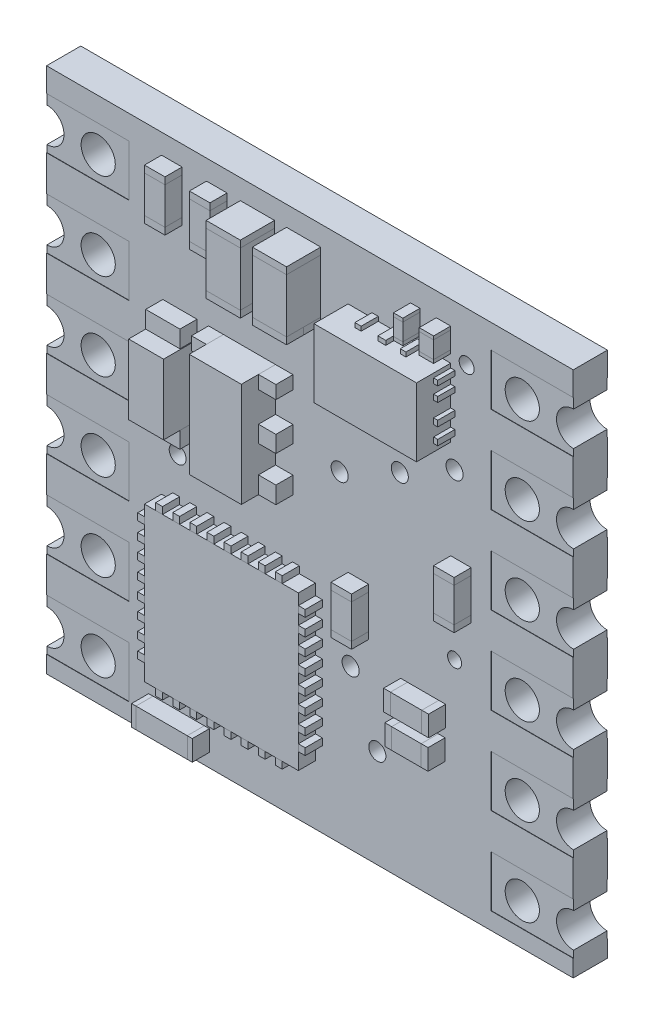
SolidWorks part; units mm, degrees
ref_plane "前视基准面" through (0, 0, 0) normal (0, 0, 1) x (1, 0, 0)
ref_plane "上视基准面" through (0, 0, 0) normal (0, 1, 0) x (1, 0, 0)
ref_plane "右视基准面" through (0, 0, 0) normal (1, 0, 0) x (0, 0, -1)
sketch "草图1" plane through (0, 0, 0) normal (0, 0, 1) x (1, 0, 0)
  line L1 (-7.7, 7.7) -> (7.7, 7.7)
  line L2 (-7.7, 7.7) -> (-7.7, -7.7)
  line L3 (-7.7, -7.7) -> (7.7, -7.7)
  line L4 (7.7, 7.7) -> (7.7, -7.7)
  line L5 (-7.7, 7.7) -> (7.7, -7.7) construction
  line L6 (-7.7, -7.7) -> (7.7, 7.7) construction
  point P0 (0, 0)
extrude "凸台-拉伸1" add sketch "草图1" along normal blind 1
sketch "草图2" plane through (0, 0, 1) normal (0, 0, 1) x (1, 0, 0)
  line L0 (-6.2, 7.7) -> (-6.2, -7.7) construction
  line L1 (7.7, 7.7) -> (-7.7, 7.7) construction
  line L2 (-7.7, -7.7) -> (7.7, -7.7) construction
  line L3 (0, 7.7) -> (0, -7.7) construction
  line L4 (-7.7, 7.7) -> (-7.7, -7.7) construction
  circle A0 centre (-6.2, 6.2) radius 0.5
  circle A1 centre (-6.2, 3.66) radius 0.5
  circle A2 centre (-6.2, 1.12) radius 0.5
  circle A3 centre (-6.2, -1.42) radius 0.5
  circle A4 centre (-6.2, -3.96) radius 0.5
  circle A5 centre (-6.2, -6.5) radius 0.5
  circle A6 centre (-7.7, 6.2) radius 0.5
  circle A7 centre (-7.7, 3.66) radius 0.5
  circle A8 centre (-7.7, 1.12) radius 0.5
  circle A9 centre (-7.7, -1.42) radius 0.5
  circle A10 centre (-7.7, -3.96) radius 0.5
  circle A11 centre (-7.7, -6.5) radius 0.5
  circle A12 centre (7.7, -6.5) radius 0.5
  circle A13 centre (7.7, -3.96) radius 0.5
  circle A14 centre (7.7, -1.42) radius 0.5
  circle A15 centre (7.7, 1.12) radius 0.5
  circle A16 centre (7.7, 3.66) radius 0.5
  circle A17 centre (7.7, 6.2) radius 0.5
  circle A18 centre (6.2, -6.5) radius 0.5
  circle A19 centre (6.2, -3.96) radius 0.5
  circle A20 centre (6.2, -1.42) radius 0.5
  circle A21 centre (6.2, 1.12) radius 0.5
  circle A22 centre (6.2, 3.66) radius 0.5
  circle A23 centre (6.2, 6.2) radius 0.5
  dimension "D2" = 1.5
  dimension "D4" = 6
  dimension "D1" = 1.5
  dimension "D3" = 6
extrude "切除-拉伸1" cut sketch "草图2" against normal blind 1
sketch "草图3" plane through (0, 0, 1) normal (0, 0, 1) x (1, 0, 0)
  line L0 (-7.7, 7.7) -> (-7.7, 6.7) construction
  line L1 (-7.7, 6.9978) -> (-5.2945, 6.9978)
  line L2 (-7.7, 6.9978) -> (-7.7, 5.4978)
  line L3 (-7.7, 5.4978) -> (-5.2945, 5.4978)
  line L4 (-5.2945, 6.9978) -> (-5.2945, 5.4978)
  line L5 (-7.7, 4.4578) -> (-5.2945, 4.4578)
  line L6 (-7.7, 4.4578) -> (-7.7, 2.9578)
  line L7 (-7.7, 2.9578) -> (-5.2945, 2.9578)
  line L8 (-5.2945, 4.4578) -> (-5.2945, 2.9578)
  line L9 (-7.7, 1.9178) -> (-5.2945, 1.9178)
  line L10 (-7.7, 1.9178) -> (-7.7, 0.4178)
  line L11 (-7.7, 0.4178) -> (-5.2945, 0.4178)
  line L12 (-5.2945, 1.9178) -> (-5.2945, 0.4178)
  line L13 (-7.7, -0.6222) -> (-5.2945, -0.6222)
  line L14 (-7.7, -0.6222) -> (-7.7, -2.1222)
  line L15 (-7.7, -2.1222) -> (-5.2945, -2.1222)
  line L16 (-5.2945, -0.6222) -> (-5.2945, -2.1222)
  line L17 (-7.7, -3.1622) -> (-5.2945, -3.1622)
  line L18 (-7.7, -3.1622) -> (-7.7, -4.6622)
  line L19 (-7.7, -4.6622) -> (-5.2945, -4.6622)
  line L20 (-5.2945, -3.1622) -> (-5.2945, -4.6622)
  line L21 (-7.7, -5.7022) -> (-5.2945, -5.7022)
  line L22 (-7.7, -5.7022) -> (-7.7, -7.2022)
  line L23 (-7.7, -7.2022) -> (-5.2945, -7.2022)
  line L24 (-5.2945, -5.7022) -> (-5.2945, -7.2022)
  line L25 (0, 7.7) -> (0, -7.7) construction
  line L26 (7.7, 7.7) -> (-7.7, 7.7) construction
  line L27 (-7.7, -7.7) -> (7.7, -7.7) construction
  line L28 (5.2945, -5.7022) -> (5.2945, -7.2022)
  line L29 (7.7, -7.2022) -> (5.2945, -7.2022)
  line L30 (7.7, -5.7022) -> (7.7, -7.2022)
  line L31 (7.7, -5.7022) -> (5.2945, -5.7022)
  line L32 (5.2945, -3.1622) -> (5.2945, -4.6622)
  line L33 (7.7, -4.6622) -> (5.2945, -4.6622)
  line L34 (7.7, -3.1622) -> (7.7, -4.6622)
  line L35 (7.7, -3.1622) -> (5.2945, -3.1622)
  line L36 (5.2945, -0.6222) -> (5.2945, -2.1222)
  line L37 (7.7, -2.1222) -> (5.2945, -2.1222)
  line L38 (7.7, -0.6222) -> (7.7, -2.1222)
  line L39 (7.7, -0.6222) -> (5.2945, -0.6222)
  line L40 (5.2945, 1.9178) -> (5.2945, 0.4178)
  line L41 (7.7, 0.4178) -> (5.2945, 0.4178)
  line L42 (7.7, 1.9178) -> (7.7, 0.4178)
  line L43 (7.7, 1.9178) -> (5.2945, 1.9178)
  line L44 (5.2945, 4.4578) -> (5.2945, 2.9578)
  line L45 (7.7, 2.9578) -> (5.2945, 2.9578)
  line L46 (7.7, 4.4578) -> (7.7, 2.9578)
  line L47 (7.7, 4.4578) -> (5.2945, 4.4578)
  line L48 (5.2945, 6.9978) -> (5.2945, 5.4978)
  line L49 (7.7, 5.4978) -> (5.2945, 5.4978)
  line L50 (7.7, 6.9978) -> (7.7, 5.4978)
  line L51 (7.7, 6.9978) -> (5.2945, 6.9978)
  dimension "D1" = 6
extrude "切除-拉伸2" cut sketch "草图3" against normal blind 0.01
extrude "切除-拉伸3" cut sketch "草图3<2>" along normal blind 0.01 from surface starting at face at (-5.7, 3.66, 0)
sketch "草图3<2>" plane through (0, 0, 1) normal (0, 0, 1) x (1, 0, 0) same geometry as "草图3"
sketch "草图4" plane through (0, 0, 1) normal (0, 0, 1) x (1, 0, 0)
  line L1 (-4.3375, -1.4674) -> (0.1625, -1.4674)
  line L2 (-4.3375, -1.4674) -> (-4.3375, -5.9674)
  line L3 (-4.3375, -5.9674) -> (0.1625, -5.9674)
  line L4 (0.1625, -1.4674) -> (0.1625, -5.9674)
  line L5 (-4.3375, -1.4674) -> (0.1625, -5.9674) construction
  line L6 (-4.3375, -5.9674) -> (0.1625, -1.4674) construction
  line L7 (1.1166, 6.0772) -> (4.1166, 6.0772)
  line L8 (1.1166, 6.0772) -> (1.1166, 4.0772)
  line L9 (1.1166, 4.0772) -> (4.1166, 4.0772)
  line L10 (4.1166, 6.0772) -> (4.1166, 4.0772)
  line L11 (1.1166, 6.0772) -> (4.1166, 4.0772) construction
  line L12 (1.1166, 4.0772) -> (4.1166, 6.0772) construction
  line L13 (-2.5272, 3.4812) -> (-1.005, 3.4812)
  line L14 (-2.5272, 3.4812) -> (-2.5272, 0.4367)
  line L15 (-2.5272, 0.4367) -> (-1.005, 0.4367)
  line L16 (-1.005, 3.4812) -> (-1.005, 0.4367)
  line L17 (-2.5272, 3.4812) -> (-1.005, 0.4367) construction
  line L18 (-2.5272, 0.4367) -> (-1.005, 3.4812) construction
  line L19 (-4.3009, 2.9812) -> (-3.2787, 2.9812)
  line L20 (-4.3009, 2.9812) -> (-4.3009, 0.9367)
  line L21 (-4.3009, 0.9367) -> (-3.2787, 0.9367)
  line L22 (-3.2787, 2.9812) -> (-3.2787, 0.9367)
  line L23 (-4.3009, 2.9812) -> (-3.2787, 0.9367) construction
  line L24 (-4.3009, 0.9367) -> (-3.2787, 2.9812) construction
  line L25 (-4.3375, 6.9169) -> (-3.7375, 6.9169)
  line L26 (-4.3375, 6.9169) -> (-4.3375, 5.841)
  line L27 (-4.3375, 5.841) -> (-3.7375, 5.841)
  line L28 (-3.7375, 6.9169) -> (-3.7375, 5.841)
  line L29 (-3.0228, 6.9169) -> (-2.4228, 6.9169)
  line L30 (-3.0228, 6.9169) -> (-3.0228, 5.841)
  line L31 (-3.0228, 5.841) -> (-2.4228, 5.841)
  line L32 (-2.4228, 6.9169) -> (-2.4228, 5.841)
  line L33 (-2.0346, 6.9169) -> (-1.0346, 6.9169)
  line L34 (-2.0346, 6.9169) -> (-2.0346, 5.341)
  line L35 (-2.0346, 5.341) -> (-1.0346, 5.341)
  line L36 (-1.0346, 6.9169) -> (-1.0346, 5.341)
  line L37 (-0.683, 6.9169) -> (0.317, 6.9169)
  line L38 (-0.683, 6.9169) -> (-0.683, 5.341)
  line L39 (-0.683, 5.341) -> (0.317, 5.341)
  line L40 (0.317, 6.9169) -> (0.317, 5.341)
  line L41 (2.9433, 6.9169) -> (3.2171, 6.9169)
  line L42 (2.9433, 6.9169) -> (2.9433, 6.4169)
  line L43 (2.9433, 6.4169) -> (3.2171, 6.4169)
  line L44 (3.2171, 6.9169) -> (3.2171, 6.4169)
  line L45 (3.6962, 6.9169) -> (4.1166, 6.9169)
  line L46 (3.6962, 6.9169) -> (3.6962, 6.4169)
  line L47 (3.6962, 6.4169) -> (4.1166, 6.4169)
  line L48 (4.1166, 6.9169) -> (4.1166, 6.4169)
  line L49 (1.1166, -0.9197) -> (1.7166, -0.9197)
  line L50 (1.1166, -0.9197) -> (1.1166, -1.9197)
  line L51 (1.1166, -1.9197) -> (1.7166, -1.9197)
  line L52 (1.7166, -0.9197) -> (1.7166, -1.9197)
  line L53 (2.8541, -2.6342) -> (3.7697, -2.6342)
  line L54 (2.8541, -2.6342) -> (2.8541, -3.2342)
  line L55 (2.8541, -3.2342) -> (3.7697, -3.2342)
  line L56 (3.7697, -2.6342) -> (3.7697, -3.2342)
  line L57 (2.8906, -3.4898) -> (3.7537, -3.4898)
  line L58 (2.8906, -3.4898) -> (2.8906, -4.0898)
  line L59 (2.8906, -4.0898) -> (3.7537, -4.0898)
  line L60 (3.7537, -3.4898) -> (3.7537, -4.0898)
  line L61 (-4.5861, -6.7069) -> (-3.0861, -6.7069)
  line L62 (-4.5861, -6.7069) -> (-4.5861, -7.3069)
  line L63 (-4.5861, -7.3069) -> (-3.0861, -7.3069)
  line L64 (-3.0861, -6.7069) -> (-3.0861, -7.3069)
  line L65 (4.1166, 1) -> (4.7166, 1)
  line L66 (4.1166, 1) -> (4.1166, 0)
  line L67 (4.1166, 0) -> (4.7166, 0)
  line L68 (4.7166, 1) -> (4.7166, 0)
  point P0 (-2.0875, -3.7174)
  point P6 (2.6166, 5.0772)
  point P11 (-1.7661, 1.959)
  point P16 (-3.7898, 1.959)
extrude "凸台-拉伸2" add sketch "草图4" along normal blind 1 contours L16 L13 L14 L15 | L10 L7 L8 L9 region at (2.6166, 5.0772, 1) region at (-1.7661, 1.959, 1)
extrude "凸台-拉伸3" add sketch "草图4<3>" along normal blind 0.5 contours L4 L1 L2 L3 | L28 L27 L26 L25 region at (-2.0875, -3.7174, 1)
sketch "草图4<3>" plane through (0, 0, 1) normal (0, 0, 1) x (1, 0, 0) same geometry as "草图4"
extrude "凸台-拉伸4" add sketch "草图4<4>" along normal blind 0.5 contours L32 L29 L30 L31 | L56 L53 L54 L55 | L60 L57 L58 L59 | L52 L49 L50 L51 | L68 L65 L66 L67 | L64 L61 L62 L63 | L48 L45 L46 L47 | L44 L41 L42 L43 | L42 L43 L44 L41 | L46 L47 L48 L45 | L68 L67 L66 L65 region at (-2.7228, 6.379, 1) region at (3.0802, 6.6669, 1) region at (3.9064, 6.6669, 1) region at (1.4166, -1.4197, 1) region at (3.3119, -2.9342, 1) region at (3.3221, -3.7898, 1) region at (-3.8361, -7.0069, 1) region at (4.4166, 0.5, 1)
sketch "草图4<4>" plane through (0, 0, 1) normal (0, 0, 1) x (1, 0, 0) same geometry as "草图4"
extrude "凸台-拉伸5" add sketch "草图4<5>" along normal blind 1 contours L36 L33 L34 L35 | L38 L39 L40 L37 region at (-1.5346, 6.129, 1)
sketch "草图4<5>" plane through (0, 0, 1) normal (0, 0, 1) x (1, 0, 0) same geometry as "草图4"
extrude "凸台-拉伸6" add sketch "草图4<6>" along normal blind 1 contours L20 L21 L22 L19
sketch "草图4<6>" plane through (0, 0, 1) normal (0, 0, 1) x (1, 0, 0) same geometry as "草图4"
sketch "草图5" plane through (0, 0, 1) normal (0, 0, 1) x (1, 0, 0)
  line L0 (-2.5272, 3.4812) -> (-2.5272, 0.4367) construction
  line L1 (-4.3009, 2.9812) -> (-3.3009, 2.9812)
  line L2 (-4.3009, 2.9812) -> (-4.3009, 3.4812)
  line L3 (-4.3009, 3.4812) -> (-3.3009, 3.4812)
  line L4 (-3.3009, 2.9812) -> (-3.3009, 3.4812)
  line L5 (-4.3009, 0.9367) -> (-3.3009, 0.9367)
  line L6 (-4.3009, 0.9367) -> (-4.3009, 0.4367)
  line L7 (-4.3009, 0.4367) -> (-3.3009, 0.4367)
  line L8 (-3.3009, 0.9367) -> (-3.3009, 0.4367)
  line L9 (-2.5272, 3.4812) -> (-2.9625, 3.4812)
  line L10 (-2.5272, 3.4812) -> (-2.5272, 3.0965)
  line L11 (-2.5272, 3.0965) -> (-2.9625, 3.0965)
  line L12 (-2.9625, 3.4812) -> (-2.9625, 3.0965)
  line L13 (-2.5272, 0.9367) -> (-2.9625, 0.9367)
  line L14 (-2.5272, 0.9367) -> (-2.5272, 0.4367)
  line L15 (-2.5272, 0.4367) -> (-2.9625, 0.4367)
  line L16 (-2.9625, 0.9367) -> (-2.9625, 0.4367)
  line L17 (-1.005, 3.4812) -> (-1.005, 0.4367) construction
  line L18 (-1.005, 3.4812) -> (-0.4936, 3.4812)
  line L19 (-1.005, 3.4812) -> (-1.005, 3.0965)
  line L20 (-1.005, 3.0965) -> (-0.4936, 3.0965)
  line L21 (-0.4936, 3.4812) -> (-0.4936, 3.0965)
  line L22 (-1.005, 2.2194) -> (-0.4936, 2.2194)
  line L23 (-1.005, 2.2194) -> (-1.005, 1.7322)
  line L24 (-1.005, 1.7322) -> (-0.4936, 1.7322)
  line L25 (-0.4936, 2.2194) -> (-0.4936, 1.7322)
  line L26 (-4.3375, 6.9169) -> (-4.3375, 5.841) construction
  line L27 (-1.005, 0.9367) -> (-0.4936, 0.9367)
  line L28 (-1.005, 0.9367) -> (-1.005, 0.4367)
  line L29 (-1.005, 0.4367) -> (-0.4936, 0.4367)
  line L30 (-0.4936, 0.9367) -> (-0.4936, 0.4367)
  line L31 (-3.7375, 5.841) -> (-4.3375, 5.841)
  line L32 (-3.7375, 5.841) -> (-3.7375, 5.641)
  line L33 (-3.7375, 5.641) -> (-4.3375, 5.641)
  line L34 (-4.3375, 5.841) -> (-4.3375, 5.641)
  line L35 (-3.7375, 6.9169) -> (-3.7375, 5.841) construction
  line L36 (-4.3375, 6.9169) -> (-3.7375, 6.9169)
  line L37 (-4.3375, 6.9169) -> (-4.3375, 7.1169)
  line L38 (-4.3375, 7.1169) -> (-3.7375, 7.1169)
  line L39 (-3.7375, 6.9169) -> (-3.7375, 7.1169)
  line L40 (-2.4228, 6.9169) -> (-2.4228, 5.841) construction
  line L41 (-3.0228, 6.9169) -> (-2.4228, 6.9169)
  line L42 (-3.0228, 6.9169) -> (-3.0228, 7.1169)
  line L43 (-3.0228, 7.1169) -> (-2.4228, 7.1169)
  line L44 (-2.4228, 6.9169) -> (-2.4228, 7.1169)
  line L45 (-2.4228, 6.9169) -> (-2.4228, 5.841) construction
  line L46 (-3.0228, 5.841) -> (-2.4228, 5.841)
  line L47 (-3.0228, 5.841) -> (-3.0228, 5.641)
  line L48 (-3.0228, 5.641) -> (-2.4228, 5.641)
  line L49 (-2.4228, 5.841) -> (-2.4228, 5.641)
  line L50 (-1.0346, 6.9169) -> (-1.0346, 5.341) construction
  line L51 (-2.0346, 6.9169) -> (-1.0346, 6.9169)
  line L52 (-2.0346, 6.9169) -> (-2.0346, 7.1169)
  line L53 (-2.0346, 7.1169) -> (-1.0346, 7.1169)
  line L54 (-1.0346, 6.9169) -> (-1.0346, 7.1169)
  line L55 (0.317, 6.9169) -> (0.317, 5.341) construction
  line L56 (-2.0346, 5.341) -> (-1.0346, 5.341)
  line L57 (-2.0346, 5.341) -> (-2.0346, 5.141)
  line L58 (-2.0346, 5.141) -> (-1.0346, 5.141)
  line L59 (-1.0346, 5.341) -> (-1.0346, 5.141)
  line L60 (-0.683, 6.9169) -> (0.317, 6.9169)
  line L61 (-0.683, 6.9169) -> (-0.683, 7.1169)
  line L62 (-0.683, 7.1169) -> (0.317, 7.1169)
  line L63 (0.317, 6.9169) -> (0.317, 7.1169)
  line L64 (-0.683, 6.9169) -> (-0.683, 5.341) construction
  line L65 (-0.683, 5.141) -> (0.317, 5.141)
  line L66 (-0.683, 5.141) -> (-0.683, 5.341)
  line L67 (-0.683, 5.341) -> (0.317, 5.341)
  line L68 (0.317, 5.141) -> (0.317, 5.341)
  line L69 (3.2171, 6.9169) -> (3.2171, 6.4169) construction
  line L70 (2.9433, 6.9169) -> (3.2171, 6.9169)
  line L71 (2.9433, 6.9169) -> (2.9433, 7.0169)
  line L72 (2.9433, 7.0169) -> (3.2171, 7.0169)
  line L73 (3.2171, 6.9169) -> (3.2171, 7.0169)
  line L74 (3.2171, 6.9169) -> (3.2171, 6.4169) construction
  line L75 (2.9433, 6.4169) -> (3.2171, 6.4169)
  line L76 (2.9433, 6.4169) -> (2.9433, 6.3169)
  line L77 (2.9433, 6.3169) -> (3.2171, 6.3169)
  line L78 (3.2171, 6.4169) -> (3.2171, 6.3169)
  line L79 (4.1166, 6.9169) -> (4.1166, 6.4169) construction
  line L80 (3.6962, 6.9169) -> (4.1166, 6.9169)
  line L81 (3.6962, 6.9169) -> (3.6962, 7.0169)
  line L82 (3.6962, 7.0169) -> (4.1166, 7.0169)
  line L83 (4.1166, 6.9169) -> (4.1166, 7.0169)
  line L84 (1.1166, 6.0772) -> (1.1166, 4.0772) construction
  line L85 (3.6962, 6.4169) -> (4.1166, 6.4169)
  line L86 (3.6962, 6.4169) -> (3.6962, 6.3169)
  line L87 (3.6962, 6.3169) -> (4.1166, 6.3169)
  line L88 (4.1166, 6.4169) -> (4.1166, 6.3169)
  line L89 (1.1166, 5.9535) -> (1.0044, 5.9535)
  line L90 (1.1166, 5.9535) -> (1.1166, 5.8087)
  line L91 (1.1166, 5.8087) -> (1.0044, 5.8087)
  line L92 (1.0044, 5.9535) -> (1.0044, 5.8087)
  line L93 (1.1166, 5.5442) -> (1.0044, 5.5442)
  line L94 (1.1166, 5.5442) -> (1.1166, 5.3892)
  line L95 (1.1166, 5.3892) -> (1.0044, 5.3892)
  line L96 (1.0044, 5.5442) -> (1.0044, 5.3892)
  line L97 (4.7166, 1) -> (4.7166, 0) construction
  line L98 (1.1166, 4.9426) -> (1.0044, 4.9426)
  line L99 (1.1166, 4.9426) -> (1.1166, 4.772)
  line L100 (1.1166, 4.772) -> (1.0044, 4.772)
  line L101 (1.0044, 4.9426) -> (1.0044, 4.772)
  line L102 (1.1166, 4.0772) -> (4.1166, 4.0772) construction
  line L103 (1.1166, 4.4587) -> (1.0044, 4.4587)
  line L104 (1.1166, 4.4587) -> (1.1166, 4.2929)
  line L105 (1.1166, 4.2929) -> (1.0044, 4.2929)
  line L106 (1.0044, 4.4587) -> (1.0044, 4.2929)
  line L107 (1.8152, 4.0772) -> (1.9994, 4.0772)
  line L108 (1.8152, 4.0772) -> (1.8152, 3.9336)
  line L109 (1.8152, 3.9336) -> (1.9994, 3.9336)
  line L110 (1.9994, 4.0772) -> (1.9994, 3.9336)
  line L111 (1.1166, 4.0772) -> (4.1166, 4.0772) construction
  line L112 (2.4877, 4.0772) -> (2.718, 4.0772)
  line L113 (2.4877, 4.0772) -> (2.4877, 3.9336)
  line L114 (2.4877, 3.9336) -> (2.718, 3.9336)
  line L115 (2.718, 4.0772) -> (2.718, 3.9336)
  line L116 (4.1166, 6.0772) -> (4.1166, 4.0772) construction
  line L117 (3.1418, 4.0772) -> (3.3077, 4.0772)
  line L118 (3.1418, 4.0772) -> (3.1418, 3.9336)
  line L119 (3.1418, 3.9336) -> (3.3077, 3.9336)
  line L120 (3.3077, 4.0772) -> (3.3077, 3.9336)
  line L125 (4.1166, 5.5442) -> (4.2382, 5.5442)
  line L126 (4.1166, 5.5442) -> (4.1166, 5.3892)
  line L127 (4.1166, 5.3892) -> (4.2382, 5.3892)
  line L128 (4.2382, 5.5442) -> (4.2382, 5.3892)
  line L129 (4.1166, 6.0772) -> (4.1166, 4.0772) construction
  line L130 (4.1166, 5.9535) -> (4.2382, 5.9535)
  line L131 (4.1166, 5.9535) -> (4.1166, 5.8087)
  line L132 (4.1166, 5.8087) -> (4.2382, 5.8087)
  line L133 (4.2382, 5.9535) -> (4.2382, 5.8087)
  line L134 (1.1166, 6.0772) -> (4.1166, 6.0772) construction
  line L135 (4.1166, 4.9426) -> (4.2382, 4.9426)
  line L136 (4.1166, 4.9426) -> (4.1166, 4.772)
  line L137 (4.1166, 4.772) -> (4.2382, 4.772)
  line L138 (4.2382, 4.9426) -> (4.2382, 4.772)
  line L139 (4.1166, 4.4587) -> (4.2382, 4.4587)
  line L140 (4.1166, 4.4587) -> (4.1166, 4.2929)
  line L141 (4.1166, 4.2929) -> (4.2382, 4.2929)
  line L142 (4.2382, 4.4587) -> (4.2382, 4.2929)
  line L143 (1.8152, 6.0772) -> (1.9994, 6.0772)
  line L144 (1.8152, 6.0772) -> (1.8152, 6.2054)
  line L145 (1.8152, 6.2054) -> (1.9994, 6.2054)
  line L146 (1.9994, 6.0772) -> (1.9994, 6.2054)
  line L147 (1.1166, 6.0772) -> (4.1166, 6.0772) construction
  line L148 (2.4877, 6.0772) -> (2.718, 6.0772)
  line L149 (2.4877, 6.0772) -> (2.4877, 6.2054)
  line L150 (2.4877, 6.2054) -> (2.718, 6.2054)
  line L151 (2.718, 6.0772) -> (2.718, 6.2054)
  line L152 (3.1418, 6.0772) -> (3.3077, 6.0772)
  line L153 (3.1418, 6.0772) -> (3.1418, 6.2054)
  line L154 (3.1418, 6.2054) -> (3.3077, 6.2054)
  line L155 (3.3077, 6.0772) -> (3.3077, 6.2054)
  line L156 (4.7166, 1) -> (4.7166, 0) construction
  line L157 (4.1166, 1) -> (4.7166, 1)
  line L158 (4.1166, 1) -> (4.1166, 1.2)
  line L159 (4.1166, 1.2) -> (4.7166, 1.2)
  line L160 (4.7166, 1) -> (4.7166, 1.2)
  line L161 (4.1166, 0) -> (4.7166, 0)
  line L162 (4.1166, 0) -> (4.1166, -0.2)
  line L163 (4.1166, -0.2) -> (4.7166, -0.2)
  line L164 (4.7166, 0) -> (4.7166, -0.2)
  line L165 (1.7166, -0.9197) -> (1.7166, -1.9197) construction
  line L166 (1.1166, -0.9197) -> (1.7166, -0.9197)
  line L167 (1.1166, -0.9197) -> (1.1166, -0.7197)
  line L168 (1.1166, -0.7197) -> (1.7166, -0.7197)
  line L169 (1.7166, -0.9197) -> (1.7166, -0.7197)
  line L170 (1.7166, -0.9197) -> (1.7166, -1.9197) construction
  line L171 (1.1166, -1.9197) -> (1.7166, -1.9197)
  line L172 (1.1166, -1.9197) -> (1.1166, -2.1197)
  line L173 (1.1166, -2.1197) -> (1.7166, -2.1197)
  line L174 (1.7166, -1.9197) -> (1.7166, -2.1197)
  line L175 (2.8541, -3.2342) -> (3.7697, -3.2342) construction
  line L176 (2.8541, -2.6342) -> (2.6541, -2.6342)
  line L177 (2.8541, -2.6342) -> (2.8541, -3.2342)
  line L178 (2.8541, -3.2342) -> (2.6541, -3.2342)
  line L179 (2.6541, -2.6342) -> (2.6541, -3.2342)
  line L180 (2.8541, -2.6342) -> (3.7697, -2.6342) construction
  line L181 (3.7697, -3.2342) -> (3.9697, -3.2342)
  line L182 (3.7697, -3.2342) -> (3.7697, -2.6342)
  line L183 (3.7697, -2.6342) -> (3.9697, -2.6342)
  line L184 (3.9697, -3.2342) -> (3.9697, -2.6342)
  line L185 (2.8906, -4.0898) -> (3.7537, -4.0898) construction
  line L186 (2.8906, -3.4898) -> (2.6906, -3.4898)
  line L187 (2.8906, -3.4898) -> (2.8906, -4.0898)
  line L188 (2.8906, -4.0898) -> (2.6906, -4.0898)
  line L189 (2.6906, -3.4898) -> (2.6906, -4.0898)
  line L190 (2.8906, -3.4898) -> (3.7537, -3.4898) construction
  line L191 (3.7537, -4.0898) -> (3.9537, -4.0898)
  line L192 (3.7537, -4.0898) -> (3.7537, -3.4898)
  line L193 (3.7537, -3.4898) -> (3.9537, -3.4898)
  line L194 (3.9537, -4.0898) -> (3.9537, -3.4898)
  line L195 (-4.5861, -7.3069) -> (-3.0861, -7.3069) construction
  line L196 (-3.0861, -6.7069) -> (-2.9395, -6.7069)
  line L197 (-3.0861, -6.7069) -> (-3.0861, -7.3069)
  line L198 (-3.0861, -7.3069) -> (-2.9395, -7.3069)
  line L199 (-2.9395, -6.7069) -> (-2.9395, -7.3069)
  line L200 (-4.3375, -5.9674) -> (0.1625, -5.9674) construction
  line L201 (-4.5861, -6.7069) -> (-4.7149, -6.7069)
  line L202 (-4.5861, -6.7069) -> (-4.5861, -7.3069)
  line L203 (-4.5861, -7.3069) -> (-4.7149, -7.3069)
  line L204 (-4.7149, -6.7069) -> (-4.7149, -7.3069)
  line L205 (-4.0096, -5.9674) -> (-3.8096, -5.9674)
  line L206 (-4.0096, -5.9674) -> (-4.0096, -6.1674)
  line L207 (-4.0096, -6.1674) -> (-3.8096, -6.1674)
  line L208 (-3.8096, -5.9674) -> (-3.8096, -6.1674)
  line L209 (-4.3375, -1.4674) -> (-4.3375, -5.9674) construction
  line L210 (-4.3375, -5.4883) -> (-4.5375, -5.4883)
  line L211 (-4.3375, -5.4883) -> (-4.3375, -5.2883)
  line L212 (-4.3375, -5.2883) -> (-4.5375, -5.2883)
  line L213 (-4.5375, -5.4883) -> (-4.5375, -5.2883)
  line L214 (-3.5096, -5.9674) -> (-3.3096, -5.9674)
  line L215 (-3.5096, -5.9674) -> (-3.5096, -6.1674)
  line L216 (-3.5096, -6.1674) -> (-3.3096, -6.1674)
  line L217 (-3.3096, -5.9674) -> (-3.3096, -6.1674)
  line L218 (-3.0096, -5.9674) -> (-2.8096, -5.9674)
  line L219 (-3.0096, -5.9674) -> (-3.0096, -6.1674)
  line L220 (-3.0096, -6.1674) -> (-2.8096, -6.1674)
  line L221 (-2.8096, -5.9674) -> (-2.8096, -6.1674)
  line L222 (-2.5096, -5.9674) -> (-2.3096, -5.9674)
  line L223 (-2.5096, -5.9674) -> (-2.5096, -6.1674)
  line L224 (-2.5096, -6.1674) -> (-2.3096, -6.1674)
  line L225 (-2.3096, -5.9674) -> (-2.3096, -6.1674)
  line L226 (-2.0096, -5.9674) -> (-1.8096, -5.9674)
  line L227 (-2.0096, -5.9674) -> (-2.0096, -6.1674)
  line L228 (-2.0096, -6.1674) -> (-1.8096, -6.1674)
  line L229 (-1.8096, -5.9674) -> (-1.8096, -6.1674)
  line L230 (-1.5096, -5.9674) -> (-1.3096, -5.9674)
  line L231 (-1.5096, -5.9674) -> (-1.5096, -6.1674)
  line L232 (-1.5096, -6.1674) -> (-1.3096, -6.1674)
  line L233 (-1.3096, -5.9674) -> (-1.3096, -6.1674)
  line L234 (-1.0096, -5.9674) -> (-0.8096, -5.9674)
  line L235 (-1.0096, -5.9674) -> (-1.0096, -6.1674)
  line L236 (-1.0096, -6.1674) -> (-0.8096, -6.1674)
  line L237 (-0.8096, -5.9674) -> (-0.8096, -6.1674)
  line L238 (-0.5096, -5.9674) -> (-0.3096, -5.9674)
  line L239 (-0.5096, -5.9674) -> (-0.5096, -6.1674)
  line L240 (-0.5096, -6.1674) -> (-0.3096, -6.1674)
  line L241 (-0.3096, -5.9674) -> (-0.3096, -6.1674)
  line L242 (-4.3375, -4.9883) -> (-4.5375, -4.9883)
  line L243 (-4.3375, -4.9883) -> (-4.3375, -4.7883)
  line L244 (-4.3375, -4.7883) -> (-4.5375, -4.7883)
  line L245 (-4.5375, -4.9883) -> (-4.5375, -4.7883)
  line L246 (-4.3375, -4.4883) -> (-4.5375, -4.4883)
  line L247 (-4.3375, -4.4883) -> (-4.3375, -4.2883)
  line L248 (-4.3375, -4.2883) -> (-4.5375, -4.2883)
  line L249 (-4.5375, -4.4883) -> (-4.5375, -4.2883)
  line L250 (-4.3375, -3.9883) -> (-4.5375, -3.9883)
  line L251 (-4.3375, -3.9883) -> (-4.3375, -3.7883)
  line L252 (-4.3375, -3.7883) -> (-4.5375, -3.7883)
  line L253 (-4.5375, -3.9883) -> (-4.5375, -3.7883)
  line L254 (-4.3375, -3.4883) -> (-4.5375, -3.4883)
  line L255 (-4.3375, -3.4883) -> (-4.3375, -3.2883)
  line L256 (-4.3375, -3.2883) -> (-4.5375, -3.2883)
  line L257 (-4.5375, -3.4883) -> (-4.5375, -3.2883)
  line L258 (-4.3375, -2.9883) -> (-4.5375, -2.9883)
  line L259 (-4.3375, -2.9883) -> (-4.3375, -2.7883)
  line L260 (-4.3375, -2.7883) -> (-4.5375, -2.7883)
  line L261 (-4.5375, -2.9883) -> (-4.5375, -2.7883)
  line L262 (-4.3375, -2.4883) -> (-4.5375, -2.4883)
  line L263 (-4.3375, -2.4883) -> (-4.3375, -2.2883)
  line L264 (-4.3375, -2.2883) -> (-4.5375, -2.2883)
  line L265 (-4.5375, -2.4883) -> (-4.5375, -2.2883)
  line L266 (-4.3375, -1.9883) -> (-4.5375, -1.9883)
  line L267 (-4.3375, -1.9883) -> (-4.3375, -1.7883)
  line L268 (-4.3375, -1.7883) -> (-4.5375, -1.7883)
  line L269 (-4.5375, -1.9883) -> (-4.5375, -1.7883)
  line L270 (-2.0875, -1.4674) -> (-2.0875, -5.9674) construction
  line L271 (-4.3375, -1.4674) -> (0.1625, -1.4674) construction
  line L272 (-4.3375, -5.9674) -> (0.1625, -5.9674) construction
  line L273 (0.1625, -3.7174) -> (-4.3375, -3.7174) construction
  line L274 (0.1625, -1.4674) -> (0.1625, -5.9674) construction
  line L275 (-4.3375, -1.4674) -> (-4.3375, -5.9674) construction
  line L276 (0.3625, -1.9883) -> (0.3625, -1.7883)
  line L277 (0.1625, -1.7883) -> (0.3625, -1.7883)
  line L278 (0.1625, -1.9883) -> (0.1625, -1.7883)
  line L279 (0.1625, -1.9883) -> (0.3625, -1.9883)
  line L280 (0.3625, -2.4883) -> (0.3625, -2.2883)
  line L281 (0.1625, -2.2883) -> (0.3625, -2.2883)
  line L282 (0.1625, -2.4883) -> (0.1625, -2.2883)
  line L283 (0.1625, -2.4883) -> (0.3625, -2.4883)
  line L284 (0.3625, -2.9883) -> (0.3625, -2.7883)
  line L285 (0.1625, -2.7883) -> (0.3625, -2.7883)
  line L286 (0.1625, -2.9883) -> (0.1625, -2.7883)
  line L287 (0.1625, -2.9883) -> (0.3625, -2.9883)
  line L288 (0.3625, -3.4883) -> (0.3625, -3.2883)
  line L289 (0.1625, -3.2883) -> (0.3625, -3.2883)
  line L290 (0.1625, -3.4883) -> (0.1625, -3.2883)
  line L291 (0.1625, -3.4883) -> (0.3625, -3.4883)
  line L292 (0.3625, -3.9883) -> (0.3625, -3.7883)
  line L293 (0.1625, -3.7883) -> (0.3625, -3.7883)
  line L294 (0.1625, -3.9883) -> (0.1625, -3.7883)
  line L295 (0.1625, -3.9883) -> (0.3625, -3.9883)
  line L296 (0.3625, -4.4883) -> (0.3625, -4.2883)
  line L297 (0.1625, -4.2883) -> (0.3625, -4.2883)
  line L298 (0.1625, -4.4883) -> (0.1625, -4.2883)
  line L299 (0.1625, -4.4883) -> (0.3625, -4.4883)
  line L300 (0.3625, -4.9883) -> (0.3625, -4.7883)
  line L301 (0.1625, -4.7883) -> (0.3625, -4.7883)
  line L302 (0.1625, -4.9883) -> (0.1625, -4.7883)
  line L303 (0.1625, -4.9883) -> (0.3625, -4.9883)
  line L304 (0.3625, -5.4883) -> (0.3625, -5.2883)
  line L305 (0.1625, -5.2883) -> (0.3625, -5.2883)
  line L306 (0.1625, -5.4883) -> (0.1625, -5.2883)
  line L307 (0.1625, -5.4883) -> (0.3625, -5.4883)
  line L308 (-0.3096, -1.4674) -> (-0.3096, -1.2674)
  line L309 (-0.5096, -1.2674) -> (-0.3096, -1.2674)
  line L310 (-0.5096, -1.4674) -> (-0.5096, -1.2674)
  line L311 (-0.5096, -1.4674) -> (-0.3096, -1.4674)
  line L312 (-0.8096, -1.4674) -> (-0.8096, -1.2674)
  line L313 (-1.0096, -1.2674) -> (-0.8096, -1.2674)
  line L314 (-1.0096, -1.4674) -> (-1.0096, -1.2674)
  line L315 (-1.0096, -1.4674) -> (-0.8096, -1.4674)
  line L316 (-1.3096, -1.4674) -> (-1.3096, -1.2674)
  line L317 (-1.5096, -1.2674) -> (-1.3096, -1.2674)
  line L318 (-1.5096, -1.4674) -> (-1.5096, -1.2674)
  line L319 (-1.5096, -1.4674) -> (-1.3096, -1.4674)
  line L320 (-1.8096, -1.4674) -> (-1.8096, -1.2674)
  line L321 (-2.0096, -1.2674) -> (-1.8096, -1.2674)
  line L322 (-2.0096, -1.4674) -> (-2.0096, -1.2674)
  line L323 (-2.0096, -1.4674) -> (-1.8096, -1.4674)
  line L324 (-2.3096, -1.4674) -> (-2.3096, -1.2674)
  line L325 (-2.5096, -1.2674) -> (-2.3096, -1.2674)
  line L326 (-2.5096, -1.4674) -> (-2.5096, -1.2674)
  line L327 (-2.5096, -1.4674) -> (-2.3096, -1.4674)
  line L328 (-2.8096, -1.4674) -> (-2.8096, -1.2674)
  line L329 (-3.0096, -1.2674) -> (-2.8096, -1.2674)
  line L330 (-3.0096, -1.4674) -> (-3.0096, -1.2674)
  line L331 (-3.0096, -1.4674) -> (-2.8096, -1.4674)
  line L332 (-3.3096, -1.4674) -> (-3.3096, -1.2674)
  line L333 (-3.5096, -1.2674) -> (-3.3096, -1.2674)
  line L334 (-3.5096, -1.4674) -> (-3.5096, -1.2674)
  line L335 (-3.5096, -1.4674) -> (-3.3096, -1.4674)
  line L336 (-3.8096, -1.4674) -> (-3.8096, -1.2674)
  line L337 (-4.0096, -1.2674) -> (-3.8096, -1.2674)
  line L338 (-4.0096, -1.4674) -> (-4.0096, -1.2674)
  line L339 (-4.0096, -1.4674) -> (-3.8096, -1.4674)
  dimension "D1" = 8
  dimension "D2" = 8
extrude "凸台-拉伸7" add sketch "草图5" along normal blind 0.5 separate body
extrude "凸台-拉伸8" add sketch "草图5<2>" along normal blind 1 separate body contours L63 L60 L61 L62 | L56 L59 L58 L57 | L60 L63 L62 L61 | L53 L54 L51 L52 | L65 L68 L67 L66 | L56 L59 L58 L57 region at (-1.5346, 5.241, 1) region at (-0.183, 7.0169, 1)
sketch "草图5<2>" plane through (0, 0, 1) normal (0, 0, 1) x (1, 0, 0) same geometry as "草图5"
sketch "草图6" plane through (0, 0, 0) normal (0, 0, -1) x (-1, 0, 0)
  line L0 (5.0945, -3.4896) -> (2.2945, -3.4896) construction
  line L1 (5.0945, -0.8908) -> (2.2945, -0.8908) construction
  line L2 (5.0945, 1.4915) -> (2.2945, 1.4915) construction
  line L3 (5.0945, 4.0334) -> (2.2945, 4.0334) construction
  text T0 "VCC" font "Verdana" height in points 3
  text T1 "SCL" font "Verdana" height in points 3
  text T2 "SDA" font "Verdana" height in points 3
  text T3 "GND" font "Verdana" height in points 3
extrude "切除-拉伸5" cut sketch "草图6" against normal blind 0.01
sketch "草图7" plane through (0, 0, 1) normal (0, 0, 1) x (1, 0, 0)
  circle A0 centre (-3.8674, -0.2225) radius 0.2468
  circle A1 centre (1.9713, -4.8256) radius 0.25
  circle A2 centre (1.191, -3.0597) radius 0.25
  circle A3 centre (4.2301, -1.3758) radius 0.2053
  circle A4 centre (2.6284, 2.5668) radius 0.25
  circle A5 centre (0.8702, 1.7044) radius 0.25
  circle A6 centre (4.2301, 3.4293) radius 0.25
  circle A7 centre (4.5834, 6.2631) radius 0.2186
extrude "切除-拉伸6" cut sketch "草图7" against normal through all
sketch "草图8" plane through (0, 0, 0) normal (0, 0, -1) x (-1, 0, 0)
  line L0 (-2.293, 0.1198) -> (-3.7305, 0.1198) construction
  line L1 (-0.7805, -1.5691) -> (-0.7805, 3.3711) construction
  line L2 (0.5454, -0.2279) -> (2.1561, -0.2279) construction
  line L3 (-1.3052, -1.2358) -> (-2.6776, -1.2358) construction
  text T0 "<r90>→</r>"
  text T1 "<r270>→</r>" font "汉仪长仿宋体" height 3.5
  text T2 "x" font "Georgia" height in points 4
  text T3 "Y" font "Helvetica Neue" height in points 3
extrude "切除-拉伸7" cut sketch "草图8" against normal blind 0.01
